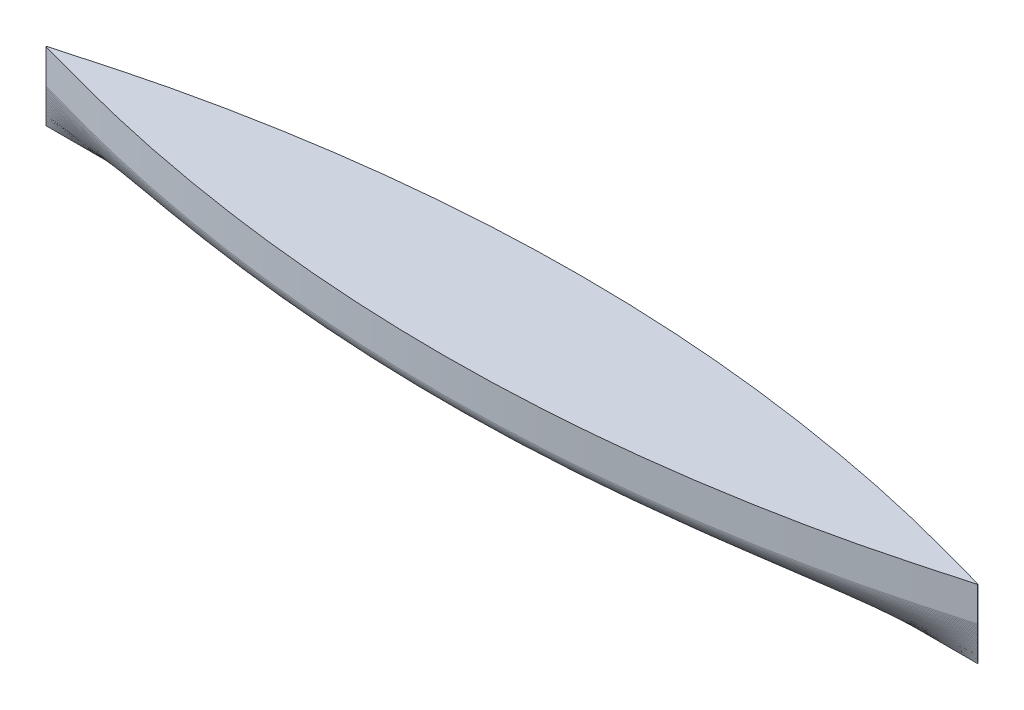
SolidWorks part; units mm, degrees
ref_plane "Plan de face" through (0, 0, 0) normal (0, 0, 1) x (1, 0, 0)
ref_plane "Plan de dessus" through (0, 0, 0) normal (0, 1, 0) x (1, 0, 0)
ref_plane "Plan de droite" through (0, 0, 0) normal (1, 0, 0) x (0, 0, -1)
ref_plane "Plan1" through (-48800, 0, 0) normal (1, 0, 0) x (0, 0, -1)
ref_plane "Plan2" through (-36600, 0, 0) normal (1, 0, 0) x (0, 0, -1)
ref_plane "Plan3" through (-24400, 0, 0) normal (1, 0, 0) x (0, 0, -1)
ref_plane "Plan4" through (-12200, 0, 0) normal (1, 0, 0) x (0, 0, -1)
ref_plane "Plan5" through (0, 0, 0) normal (1, 0, 0) x (0, 0, -1)
ref_plane "Plan6" through (12200, 0, 0) normal (1, 0, 0) x (0, 0, -1)
ref_plane "Plan7" through (24400, 0, 0) normal (1, 0, 0) x (0, 0, -1)
ref_plane "Plan8" through (36600, 0, 0) normal (1, 0, 0) x (0, 0, -1)
ref_plane "Plan9" through (48800, 0, 0) normal (1, 0, 0) x (0, 0, -1)
ref_plane "Plan10" through (-60900, 0, 0) normal (1, 0, 0) x (0, 0, -1)
ref_plane "Plan11" through (60900, 0, 0) normal (1, 0, 0) x (0, 0, -1)
sketch "Esquisse12" plane through (-60900, 0, 0) normal (1, 0, 0) x (0, 0, -1)
  line L0 (0, 0) -> (2.03, 150)
  line L1 (2.03, 150) -> (3.99, 300)
  line L2 (3.99, 300) -> (5.88, 450)
  line L3 (5.88, 450) -> (7.69, 600)
  line L4 (7.69, 600) -> (9.42, 750)
  line L5 (9.42, 750) -> (11.08, 900)
  line L6 (11.08, 900) -> (12.67, 1050)
  line L7 (12.67, 1050) -> (14.18, 1200)
  line L8 (14.18, 1200) -> (15.62, 1350)
  line L9 (15.62, 1350) -> (16.98, 1500)
  line L10 (16.98, 1500) -> (18.27, 1650)
  line L11 (18.27, 1650) -> (19.49, 1800)
  line L12 (19.49, 1800) -> (20.63, 1950)
  line L13 (20.63, 1950) -> (21.71, 2100)
  line L14 (21.71, 2100) -> (22.71, 2250)
  line L15 (22.71, 2250) -> (23.64, 2400)
  line L16 (23.64, 2400) -> (24.5, 2550)
  line L17 (24.5, 2550) -> (25.29, 2700)
  line L18 (25.29, 2700) -> (26, 2850)
  line L19 (26, 2850) -> (26.65, 3000)
  line L20 (26.65, 3000) -> (27.23, 3150)
  line L21 (27.23, 3150) -> (27.74, 3300)
  line L22 (27.74, 3300) -> (28.19, 3450)
  line L23 (28.19, 3450) -> (28.56, 3600)
  line L24 (28.56, 3600) -> (28.87, 3750)
  line L25 (28.87, 3750) -> (29.12, 3900)
  line L26 (29.12, 3900) -> (29.3, 4050)
  line L27 (29.3, 4050) -> (29.42, 4200)
  line L28 (29.42, 4200) -> (29.48, 4350)
  line L29 (29.48, 4350) -> (29.48, 4500)
  line L30 (29.48, 4500) -> (29.48, 4650)
  line L31 (29.48, 4650) -> (29.48, 4800)
  line L32 (29.48, 4800) -> (29.48, 4950)
  line L33 (29.48, 4950) -> (29.48, 5100)
  line L34 (29.48, 5100) -> (29.48, 5250)
  line L35 (29.48, 5250) -> (29.48, 5400)
  line L36 (29.48, 5400) -> (29.48, 5550)
  line L37 (29.48, 5550) -> (29.48, 5700)
  line L38 (29.48, 5700) -> (29.48, 5850)
  line L39 (29.48, 5850) -> (29.48, 6000)
  line L40 (29.48, 6000) -> (29.48, 6150)
  line L41 (29.48, 6150) -> (29.48, 6300)
  line L42 (29.48, 6300) -> (29.48, 6450)
  line L43 (29.48, 6450) -> (29.48, 6600)
  line L44 (29.48, 6600) -> (29.48, 6750)
  line L45 (29.48, 6750) -> (29.48, 6900)
  line L46 (29.48, 6900) -> (29.48, 7050)
  line L47 (29.48, 7050) -> (29.48, 7200)
  line L48 (29.48, 7200) -> (29.48, 7350)
  line L49 (29.48, 7350) -> (29.48, 7500)
  line L50 (29.48, 7500) -> (29.48, 7650)
  line L51 (29.48, 7650) -> (29.48, 7800)
  line L52 (29.48, 7800) -> (29.48, 7950)
  line L53 (29.48, 7950) -> (29.48, 8100)
  line L54 (29.48, 8100) -> (29.48, 8250)
  line L55 (29.48, 8250) -> (29.48, 8400)
  line L56 (29.48, 8400) -> (29.48, 8550)
  line L57 (29.48, 8550) -> (29.48, 8700)
  line L58 (29.48, 8700) -> (29.48, 8850)
  line L59 (29.48, 8850) -> (29.48, 9000)
  line L60 (29.48, 9000) -> (-29.48, 9000)
  line L61 (-29.48, 9000) -> (-29.48, 8850)
  line L62 (-29.48, 8850) -> (-29.48, 8700)
  line L63 (-29.48, 8700) -> (-29.48, 8550)
  line L64 (-29.48, 8550) -> (-29.48, 8400)
  line L65 (-29.48, 8400) -> (-29.48, 8250)
  line L66 (-29.48, 8250) -> (-29.48, 8100)
  line L67 (-29.48, 8100) -> (-29.48, 7950)
  line L68 (-29.48, 7950) -> (-29.48, 7800)
  line L69 (-29.48, 7800) -> (-29.48, 7650)
  line L70 (-29.48, 7650) -> (-29.48, 7500)
  line L71 (-29.48, 7500) -> (-29.48, 7350)
  line L72 (-29.48, 7350) -> (-29.48, 7200)
  line L73 (-29.48, 7200) -> (-29.48, 7050)
  line L74 (-29.48, 7050) -> (-29.48, 6900)
  line L75 (-29.48, 6900) -> (-29.48, 6750)
  line L76 (-29.48, 6750) -> (-29.48, 6600)
  line L77 (-29.48, 6600) -> (-29.48, 6450)
  line L78 (-29.48, 6450) -> (-29.48, 6300)
  line L79 (-29.48, 6300) -> (-29.48, 6150)
  line L80 (-29.48, 6150) -> (-29.48, 6000)
  line L81 (-29.48, 6000) -> (-29.48, 5850)
  line L82 (-29.48, 5850) -> (-29.48, 5700)
  line L83 (-29.48, 5700) -> (-29.48, 5550)
  line L84 (-29.48, 5550) -> (-29.48, 5400)
  line L85 (-29.48, 5400) -> (-29.48, 5250)
  line L86 (-29.48, 5250) -> (-29.48, 5100)
  line L87 (-29.48, 5100) -> (-29.48, 4950)
  line L88 (-29.48, 4950) -> (-29.48, 4800)
  line L89 (-29.48, 4800) -> (-29.48, 4650)
  line L90 (-29.48, 4650) -> (-29.48, 4500)
  line L91 (-29.48, 4500) -> (-29.48, 4350)
  line L92 (-29.48, 4350) -> (-29.42, 4200)
  line L93 (-29.42, 4200) -> (-29.3, 4050)
  line L94 (-29.3, 4050) -> (-29.12, 3900)
  line L95 (-29.12, 3900) -> (-28.87, 3750)
  line L96 (-28.87, 3750) -> (-28.56, 3600)
  line L97 (-28.56, 3600) -> (-28.19, 3450)
  line L98 (-28.19, 3450) -> (-27.74, 3300)
  line L99 (-27.74, 3300) -> (-27.23, 3150)
  line L100 (-27.23, 3150) -> (-26.65, 3000)
  line L101 (-26.65, 3000) -> (-26, 2850)
  line L102 (-26, 2850) -> (-25.29, 2700)
  line L103 (-25.29, 2700) -> (-24.5, 2550)
  line L104 (-24.5, 2550) -> (-23.64, 2400)
  line L105 (-23.64, 2400) -> (-22.71, 2250)
  line L106 (-22.71, 2250) -> (-21.71, 2100)
  line L107 (-21.71, 2100) -> (-20.63, 1950)
  line L108 (-20.63, 1950) -> (-19.49, 1800)
  line L109 (-19.49, 1800) -> (-18.27, 1650)
  line L110 (-18.27, 1650) -> (-16.98, 1500)
  line L111 (-16.98, 1500) -> (-15.62, 1350)
  line L112 (-15.62, 1350) -> (-14.18, 1200)
  line L113 (-14.18, 1200) -> (-12.67, 1050)
  line L114 (-12.67, 1050) -> (-11.08, 900)
  line L115 (-11.08, 900) -> (-9.42, 750)
  line L116 (-9.42, 750) -> (-7.69, 600)
  line L117 (-7.69, 600) -> (-5.88, 450)
  line L118 (-5.88, 450) -> (-3.99, 300)
  line L119 (-3.99, 300) -> (-2.03, 150)
  line L120 (-2.03, 150) -> (0, 0)
sketch "Esquisse15" plane through (60900, 0, 0) normal (1, 0, 0) x (0, 0, -1)
  line L0 (0, 0) -> (2.03, 150)
  line L1 (2.03, 150) -> (3.99, 300)
  line L2 (3.99, 300) -> (5.88, 450)
  line L3 (5.88, 450) -> (7.69, 600)
  line L4 (7.69, 600) -> (9.42, 750)
  line L5 (9.42, 750) -> (11.08, 900)
  line L6 (11.08, 900) -> (12.67, 1050)
  line L7 (12.67, 1050) -> (14.18, 1200)
  line L8 (14.18, 1200) -> (15.62, 1350)
  line L9 (15.62, 1350) -> (16.98, 1500)
  line L10 (16.98, 1500) -> (18.27, 1650)
  line L11 (18.27, 1650) -> (19.49, 1800)
  line L12 (19.49, 1800) -> (20.63, 1950)
  line L13 (20.63, 1950) -> (21.71, 2100)
  line L14 (21.71, 2100) -> (22.71, 2250)
  line L15 (22.71, 2250) -> (23.64, 2400)
  line L16 (23.64, 2400) -> (24.5, 2550)
  line L17 (24.5, 2550) -> (25.29, 2700)
  line L18 (25.29, 2700) -> (26, 2850)
  line L19 (26, 2850) -> (26.65, 3000)
  line L20 (26.65, 3000) -> (27.23, 3150)
  line L21 (27.23, 3150) -> (27.74, 3300)
  line L22 (27.74, 3300) -> (28.19, 3450)
  line L23 (28.19, 3450) -> (28.56, 3600)
  line L24 (28.56, 3600) -> (28.87, 3750)
  line L25 (28.87, 3750) -> (29.12, 3900)
  line L26 (29.12, 3900) -> (29.3, 4050)
  line L27 (29.3, 4050) -> (29.42, 4200)
  line L28 (29.42, 4200) -> (29.48, 4350)
  line L29 (29.48, 4350) -> (29.48, 4500)
  line L30 (29.48, 4500) -> (29.48, 4650)
  line L31 (29.48, 4650) -> (29.48, 4800)
  line L32 (29.48, 4800) -> (29.48, 4950)
  line L33 (29.48, 4950) -> (29.48, 5100)
  line L34 (29.48, 5100) -> (29.48, 5250)
  line L35 (29.48, 5250) -> (29.48, 5400)
  line L36 (29.48, 5400) -> (29.48, 5550)
  line L37 (29.48, 5550) -> (29.48, 5700)
  line L38 (29.48, 5700) -> (29.48, 5850)
  line L39 (29.48, 5850) -> (29.48, 6000)
  line L40 (29.48, 6000) -> (29.48, 6150)
  line L41 (29.48, 6150) -> (29.48, 6300)
  line L42 (29.48, 6300) -> (29.48, 6450)
  line L43 (29.48, 6450) -> (29.48, 6600)
  line L44 (29.48, 6600) -> (29.48, 6750)
  line L45 (29.48, 6750) -> (29.48, 6900)
  line L46 (29.48, 6900) -> (29.48, 7050)
  line L47 (29.48, 7050) -> (29.48, 7200)
  line L48 (29.48, 7200) -> (29.48, 7350)
  line L49 (29.48, 7350) -> (29.48, 7500)
  line L50 (29.48, 7500) -> (29.48, 7650)
  line L51 (29.48, 7650) -> (29.48, 7800)
  line L52 (29.48, 7800) -> (29.48, 7950)
  line L53 (29.48, 7950) -> (29.48, 8100)
  line L54 (29.48, 8100) -> (29.48, 8250)
  line L55 (29.48, 8250) -> (29.48, 8400)
  line L56 (29.48, 8400) -> (29.48, 8550)
  line L57 (29.48, 8550) -> (29.48, 8700)
  line L58 (29.48, 8700) -> (29.48, 8850)
  line L59 (29.48, 8850) -> (29.48, 9000)
  line L60 (29.48, 9000) -> (-29.48, 9000)
  line L61 (-29.48, 9000) -> (-29.48, 8850)
  line L62 (-29.48, 8850) -> (-29.48, 8700)
  line L63 (-29.48, 8700) -> (-29.48, 8550)
  line L64 (-29.48, 8550) -> (-29.48, 8400)
  line L65 (-29.48, 8400) -> (-29.48, 8250)
  line L66 (-29.48, 8250) -> (-29.48, 8100)
  line L67 (-29.48, 8100) -> (-29.48, 7950)
  line L68 (-29.48, 7950) -> (-29.48, 7800)
  line L69 (-29.48, 7800) -> (-29.48, 7650)
  line L70 (-29.48, 7650) -> (-29.48, 7500)
  line L71 (-29.48, 7500) -> (-29.48, 7350)
  line L72 (-29.48, 7350) -> (-29.48, 7200)
  line L73 (-29.48, 7200) -> (-29.48, 7050)
  line L74 (-29.48, 7050) -> (-29.48, 6900)
  line L75 (-29.48, 6900) -> (-29.48, 6750)
  line L76 (-29.48, 6750) -> (-29.48, 6600)
  line L77 (-29.48, 6600) -> (-29.48, 6450)
  line L78 (-29.48, 6450) -> (-29.48, 6300)
  line L79 (-29.48, 6300) -> (-29.48, 6150)
  line L80 (-29.48, 6150) -> (-29.48, 6000)
  line L81 (-29.48, 6000) -> (-29.48, 5850)
  line L82 (-29.48, 5850) -> (-29.48, 5700)
  line L83 (-29.48, 5700) -> (-29.48, 5550)
  line L84 (-29.48, 5550) -> (-29.48, 5400)
  line L85 (-29.48, 5400) -> (-29.48, 5250)
  line L86 (-29.48, 5250) -> (-29.48, 5100)
  line L87 (-29.48, 5100) -> (-29.48, 4950)
  line L88 (-29.48, 4950) -> (-29.48, 4800)
  line L89 (-29.48, 4800) -> (-29.48, 4650)
  line L90 (-29.48, 4650) -> (-29.48, 4500)
  line L91 (-29.48, 4500) -> (-29.48, 4350)
  line L92 (-29.48, 4350) -> (-29.42, 4200)
  line L93 (-29.42, 4200) -> (-29.3, 4050)
  line L94 (-29.3, 4050) -> (-29.12, 3900)
  line L95 (-29.12, 3900) -> (-28.87, 3750)
  line L96 (-28.87, 3750) -> (-28.56, 3600)
  line L97 (-28.56, 3600) -> (-28.19, 3450)
  line L98 (-28.19, 3450) -> (-27.74, 3300)
  line L99 (-27.74, 3300) -> (-27.23, 3150)
  line L100 (-27.23, 3150) -> (-26.65, 3000)
  line L101 (-26.65, 3000) -> (-26, 2850)
  line L102 (-26, 2850) -> (-25.29, 2700)
  line L103 (-25.29, 2700) -> (-24.5, 2550)
  line L104 (-24.5, 2550) -> (-23.64, 2400)
  line L105 (-23.64, 2400) -> (-22.71, 2250)
  line L106 (-22.71, 2250) -> (-21.71, 2100)
  line L107 (-21.71, 2100) -> (-20.63, 1950)
  line L108 (-20.63, 1950) -> (-19.49, 1800)
  line L109 (-19.49, 1800) -> (-18.27, 1650)
  line L110 (-18.27, 1650) -> (-16.98, 1500)
  line L111 (-16.98, 1500) -> (-15.62, 1350)
  line L112 (-15.62, 1350) -> (-14.18, 1200)
  line L113 (-14.18, 1200) -> (-12.67, 1050)
  line L114 (-12.67, 1050) -> (-11.08, 900)
  line L115 (-11.08, 900) -> (-9.42, 750)
  line L116 (-9.42, 750) -> (-7.69, 600)
  line L117 (-7.69, 600) -> (-5.88, 450)
  line L118 (-5.88, 450) -> (-3.99, 300)
  line L119 (-3.99, 300) -> (-2.03, 150)
  line L120 (-2.03, 150) -> (0, 0)
sketch "Esquisse1" plane through (-48800, 0, 0) normal (1, 0, 0) x (0, 0, -1)
  line L0 (0, 0) -> (223.61, 150)
  line L1 (223.61, 150) -> (438.92, 300)
  line L2 (438.92, 300) -> (645.97, 450)
  line L3 (645.97, 450) -> (844.77, 600)
  line L4 (844.77, 600) -> (1035.35, 750)
  line L5 (1035.35, 750) -> (1217.74, 900)
  line L6 (1217.74, 900) -> (1391.97, 1050)
  line L7 (1391.97, 1050) -> (1558.05, 1200)
  line L8 (1558.05, 1200) -> (1716.03, 1350)
  line L9 (1716.03, 1350) -> (1865.93, 1500)
  line L10 (1865.93, 1500) -> (2007.79, 1650)
  line L11 (2007.79, 1650) -> (2141.64, 1800)
  line L12 (2141.64, 1800) -> (2267.52, 1950)
  line L13 (2267.52, 1950) -> (2385.46, 2100)
  line L14 (2385.46, 2100) -> (2495.5, 2250)
  line L15 (2495.5, 2250) -> (2597.68, 2400)
  line L16 (2597.68, 2400) -> (2692.06, 2550)
  line L17 (2692.06, 2550) -> (2778.68, 2700)
  line L18 (2778.68, 2700) -> (2857.58, 2850)
  line L19 (2857.58, 2850) -> (2928.83, 3000)
  line L20 (2928.83, 3000) -> (2992.49, 3150)
  line L21 (2992.49, 3150) -> (3048.63, 3300)
  line L22 (3048.63, 3300) -> (3097.31, 3450)
  line L23 (3097.31, 3450) -> (3138.63, 3600)
  line L24 (3138.63, 3600) -> (3172.68, 3750)
  line L25 (3172.68, 3750) -> (3199.58, 3900)
  line L26 (3199.58, 3900) -> (3219.46, 4050)
  line L27 (3219.46, 4050) -> (3232.52, 4200)
  line L28 (3232.52, 4200) -> (3239.03, 4350)
  line L29 (3239.03, 4350) -> (3240, 4500)
  line L30 (3240, 4500) -> (3240, 4650)
  line L31 (3240, 4650) -> (3240, 4800)
  line L32 (3240, 4800) -> (3240, 4950)
  line L33 (3240, 4950) -> (3240, 5100)
  line L34 (3240, 5100) -> (3240, 5250)
  line L35 (3240, 5250) -> (3240, 5400)
  line L36 (3240, 5400) -> (3240, 5550)
  line L37 (3240, 5550) -> (3240, 5700)
  line L38 (3240, 5700) -> (3240, 5850)
  line L39 (3240, 5850) -> (3240, 6000)
  line L40 (3240, 6000) -> (3240, 6150)
  line L41 (3240, 6150) -> (3240, 6300)
  line L42 (3240, 6300) -> (3240, 6450)
  line L43 (3240, 6450) -> (3240, 6600)
  line L44 (3240, 6600) -> (3240, 6750)
  line L45 (3240, 6750) -> (3240, 6900)
  line L46 (3240, 6900) -> (3240, 7050)
  line L47 (3240, 7050) -> (3240, 7200)
  line L48 (3240, 7200) -> (3240, 7350)
  line L49 (3240, 7350) -> (3240, 7500)
  line L50 (3240, 7500) -> (3240, 7650)
  line L51 (3240, 7650) -> (3240, 7800)
  line L52 (3240, 7800) -> (3240, 7950)
  line L53 (3240, 7950) -> (3240, 8100)
  line L54 (3240, 8100) -> (3240, 8250)
  line L55 (3240, 8250) -> (3240, 8400)
  line L56 (3240, 8400) -> (3240, 8550)
  line L57 (3240, 8550) -> (3240, 8700)
  line L58 (3240, 8700) -> (3240, 8850)
  line L59 (3240, 8850) -> (3240, 9000)
  line L60 (3240, 9000) -> (-3240, 9000)
  line L61 (-3240, 9000) -> (-3240, 8850)
  line L62 (-3240, 8850) -> (-3240, 8700)
  line L63 (-3240, 8700) -> (-3240, 8550)
  line L64 (-3240, 8550) -> (-3240, 8400)
  line L65 (-3240, 8400) -> (-3240, 8250)
  line L66 (-3240, 8250) -> (-3240, 8100)
  line L67 (-3240, 8100) -> (-3240, 7950)
  line L68 (-3240, 7950) -> (-3240, 7800)
  line L69 (-3240, 7800) -> (-3240, 7650)
  line L70 (-3240, 7650) -> (-3240, 7500)
  line L71 (-3240, 7500) -> (-3240, 7350)
  line L72 (-3240, 7350) -> (-3240, 7200)
  line L73 (-3240, 7200) -> (-3240, 7050)
  line L74 (-3240, 7050) -> (-3240, 6900)
  line L75 (-3240, 6900) -> (-3240, 6750)
  line L76 (-3240, 6750) -> (-3240, 6600)
  line L77 (-3240, 6600) -> (-3240, 6450)
  line L78 (-3240, 6450) -> (-3240, 6300)
  line L79 (-3240, 6300) -> (-3240, 6150)
  line L80 (-3240, 6150) -> (-3240, 6000)
  line L81 (-3240, 6000) -> (-3240, 5850)
  line L82 (-3240, 5850) -> (-3240, 5700)
  line L83 (-3240, 5700) -> (-3240, 5550)
  line L84 (-3240, 5550) -> (-3240, 5400)
  line L85 (-3240, 5400) -> (-3240, 5250)
  line L86 (-3240, 5250) -> (-3240, 5100)
  line L87 (-3240, 5100) -> (-3240, 4950)
  line L88 (-3240, 4950) -> (-3240, 4800)
  line L89 (-3240, 4800) -> (-3240, 4650)
  line L90 (-3240, 4650) -> (-3240, 4500)
  line L91 (-3240, 4500) -> (-3239.03, 4350)
  line L92 (-3239.03, 4350) -> (-3232.52, 4200)
  line L93 (-3232.52, 4200) -> (-3219.46, 4050)
  line L94 (-3219.46, 4050) -> (-3199.58, 3900)
  line L95 (-3199.58, 3900) -> (-3172.68, 3750)
  line L96 (-3172.68, 3750) -> (-3138.63, 3600)
  line L97 (-3138.63, 3600) -> (-3097.31, 3450)
  line L98 (-3097.31, 3450) -> (-3048.63, 3300)
  line L99 (-3048.63, 3300) -> (-2992.49, 3150)
  line L100 (-2992.49, 3150) -> (-2928.83, 3000)
  line L101 (-2928.83, 3000) -> (-2857.58, 2850)
  line L102 (-2857.58, 2850) -> (-2778.68, 2700)
  line L103 (-2778.68, 2700) -> (-2692.06, 2550)
  line L104 (-2692.06, 2550) -> (-2597.68, 2400)
  line L105 (-2597.68, 2400) -> (-2495.5, 2250)
  line L106 (-2495.5, 2250) -> (-2385.46, 2100)
  line L107 (-2385.46, 2100) -> (-2267.52, 1950)
  line L108 (-2267.52, 1950) -> (-2141.64, 1800)
  line L109 (-2141.64, 1800) -> (-2007.79, 1650)
  line L110 (-2007.79, 1650) -> (-1865.93, 1500)
  line L111 (-1865.93, 1500) -> (-1716.03, 1350)
  line L112 (-1716.03, 1350) -> (-1558.05, 1200)
  line L113 (-1558.05, 1200) -> (-1391.97, 1050)
  line L114 (-1391.97, 1050) -> (-1217.74, 900)
  line L115 (-1217.74, 900) -> (-1035.35, 750)
  line L116 (-1035.35, 750) -> (-844.77, 600)
  line L117 (-844.77, 600) -> (-645.97, 450)
  line L118 (-645.97, 450) -> (-438.92, 300)
  line L119 (-438.92, 300) -> (-223.61, 150)
  line L120 (-223.61, 150) -> (0, 0)
sketch "Esquisse2" plane through (-36600, 0, 0) normal (1, 0, 0) x (0, 0, -1)
  line L0 (0, 0) -> (397.53, 150)
  line L1 (397.53, 150) -> (780.31, 300)
  line L2 (780.31, 300) -> (1148.39, 450)
  line L3 (1148.39, 450) -> (1501.82, 600)
  line L4 (1501.82, 600) -> (1840.63, 750)
  line L5 (1840.63, 750) -> (2164.88, 900)
  line L6 (2164.88, 900) -> (2474.61, 1050)
  line L7 (2474.61, 1050) -> (2769.87, 1200)
  line L8 (2769.87, 1200) -> (3050.72, 1350)
  line L9 (3050.72, 1350) -> (3317.22, 1500)
  line L10 (3317.22, 1500) -> (3569.41, 1650)
  line L11 (3569.41, 1650) -> (3807.36, 1800)
  line L12 (3807.36, 1800) -> (4031.14, 1950)
  line L13 (4031.14, 1950) -> (4240.81, 2100)
  line L14 (4240.81, 2100) -> (4436.44, 2250)
  line L15 (4436.44, 2250) -> (4618.1, 2400)
  line L16 (4618.1, 2400) -> (4785.89, 2550)
  line L17 (4785.89, 2550) -> (4939.87, 2700)
  line L18 (4939.87, 2700) -> (5080.15, 2850)
  line L19 (5080.15, 2850) -> (5206.82, 3000)
  line L20 (5206.82, 3000) -> (5319.99, 3150)
  line L21 (5319.99, 3150) -> (5419.78, 3300)
  line L22 (5419.78, 3300) -> (5506.33, 3450)
  line L23 (5506.33, 3450) -> (5579.79, 3600)
  line L24 (5579.79, 3600) -> (5640.32, 3750)
  line L25 (5640.32, 3750) -> (5688.14, 3900)
  line L26 (5688.14, 3900) -> (5723.49, 4050)
  line L27 (5723.49, 4050) -> (5746.7, 4200)
  line L28 (5746.7, 4200) -> (5758.27, 4350)
  line L29 (5758.27, 4350) -> (5760, 4500)
  line L30 (5760, 4500) -> (5760, 4650)
  line L31 (5760, 4650) -> (5760, 4800)
  line L32 (5760, 4800) -> (5760, 4950)
  line L33 (5760, 4950) -> (5760, 5100)
  line L34 (5760, 5100) -> (5760, 5250)
  line L35 (5760, 5250) -> (5760, 5400)
  line L36 (5760, 5400) -> (5760, 5550)
  line L37 (5760, 5550) -> (5760, 5700)
  line L38 (5760, 5700) -> (5760, 5850)
  line L39 (5760, 5850) -> (5760, 6000)
  line L40 (5760, 6000) -> (5760, 6150)
  line L41 (5760, 6150) -> (5760, 6300)
  line L42 (5760, 6300) -> (5760, 6450)
  line L43 (5760, 6450) -> (5760, 6600)
  line L44 (5760, 6600) -> (5760, 6750)
  line L45 (5760, 6750) -> (5760, 6900)
  line L46 (5760, 6900) -> (5760, 7050)
  line L47 (5760, 7050) -> (5760, 7200)
  line L48 (5760, 7200) -> (5760, 7350)
  line L49 (5760, 7350) -> (5760, 7500)
  line L50 (5760, 7500) -> (5760, 7650)
  line L51 (5760, 7650) -> (5760, 7800)
  line L52 (5760, 7800) -> (5760, 7950)
  line L53 (5760, 7950) -> (5760, 8100)
  line L54 (5760, 8100) -> (5760, 8250)
  line L55 (5760, 8250) -> (5760, 8400)
  line L56 (5760, 8400) -> (5760, 8550)
  line L57 (5760, 8550) -> (5760, 8700)
  line L58 (5760, 8700) -> (5760, 8850)
  line L59 (5760, 8850) -> (5760, 9000)
  line L60 (5760, 9000) -> (-5760, 9000)
  line L61 (-5760, 9000) -> (-5760, 8850)
  line L62 (-5760, 8850) -> (-5760, 8700)
  line L63 (-5760, 8700) -> (-5760, 8550)
  line L64 (-5760, 8550) -> (-5760, 8400)
  line L65 (-5760, 8400) -> (-5760, 8250)
  line L66 (-5760, 8250) -> (-5760, 8100)
  line L67 (-5760, 8100) -> (-5760, 7950)
  line L68 (-5760, 7950) -> (-5760, 7800)
  line L69 (-5760, 7800) -> (-5760, 7650)
  line L70 (-5760, 7650) -> (-5760, 7500)
  line L71 (-5760, 7500) -> (-5760, 7350)
  line L72 (-5760, 7350) -> (-5760, 7200)
  line L73 (-5760, 7200) -> (-5760, 7050)
  line L74 (-5760, 7050) -> (-5760, 6900)
  line L75 (-5760, 6900) -> (-5760, 6750)
  line L76 (-5760, 6750) -> (-5760, 6600)
  line L77 (-5760, 6600) -> (-5760, 6450)
  line L78 (-5760, 6450) -> (-5760, 6300)
  line L79 (-5760, 6300) -> (-5760, 6150)
  line L80 (-5760, 6150) -> (-5760, 6000)
  line L81 (-5760, 6000) -> (-5760, 5850)
  line L82 (-5760, 5850) -> (-5760, 5700)
  line L83 (-5760, 5700) -> (-5760, 5550)
  line L84 (-5760, 5550) -> (-5760, 5400)
  line L85 (-5760, 5400) -> (-5760, 5250)
  line L86 (-5760, 5250) -> (-5760, 5100)
  line L87 (-5760, 5100) -> (-5760, 4950)
  line L88 (-5760, 4950) -> (-5760, 4800)
  line L89 (-5760, 4800) -> (-5760, 4650)
  line L90 (-5760, 4650) -> (-5760, 4500)
  line L91 (-5760, 4500) -> (-5758.27, 4350)
  line L92 (-5758.27, 4350) -> (-5746.7, 4200)
  line L93 (-5746.7, 4200) -> (-5723.49, 4050)
  line L94 (-5723.49, 4050) -> (-5688.14, 3900)
  line L95 (-5688.14, 3900) -> (-5640.32, 3750)
  line L96 (-5640.32, 3750) -> (-5579.79, 3600)
  line L97 (-5579.79, 3600) -> (-5506.33, 3450)
  line L98 (-5506.33, 3450) -> (-5419.78, 3300)
  line L99 (-5419.78, 3300) -> (-5319.99, 3150)
  line L100 (-5319.99, 3150) -> (-5206.82, 3000)
  line L101 (-5206.82, 3000) -> (-5080.15, 2850)
  line L102 (-5080.15, 2850) -> (-4939.87, 2700)
  line L103 (-4939.87, 2700) -> (-4785.89, 2550)
  line L104 (-4785.89, 2550) -> (-4618.1, 2400)
  line L105 (-4618.1, 2400) -> (-4436.44, 2250)
  line L106 (-4436.44, 2250) -> (-4240.81, 2100)
  line L107 (-4240.81, 2100) -> (-4031.14, 1950)
  line L108 (-4031.14, 1950) -> (-3807.36, 1800)
  line L109 (-3807.36, 1800) -> (-3569.41, 1650)
  line L110 (-3569.41, 1650) -> (-3317.22, 1500)
  line L111 (-3317.22, 1500) -> (-3050.72, 1350)
  line L112 (-3050.72, 1350) -> (-2769.87, 1200)
  line L113 (-2769.87, 1200) -> (-2474.61, 1050)
  line L114 (-2474.61, 1050) -> (-2164.88, 900)
  line L115 (-2164.88, 900) -> (-1840.63, 750)
  line L116 (-1840.63, 750) -> (-1501.82, 600)
  line L117 (-1501.82, 600) -> (-1148.39, 450)
  line L118 (-1148.39, 450) -> (-780.31, 300)
  line L119 (-780.31, 300) -> (-397.53, 150)
  line L120 (-397.53, 150) -> (0, 0)
sketch "Esquisse3" plane through (-24400, 0, 0) normal (1, 0, 0) x (0, 0, -1)
  line L0 (0, 0) -> (521.75, 150)
  line L1 (521.75, 150) -> (1024.16, 300)
  line L2 (1024.16, 300) -> (1507.26, 450)
  line L3 (1507.26, 450) -> (1971.13, 600)
  line L4 (1971.13, 600) -> (2415.82, 750)
  line L5 (2415.82, 750) -> (2841.4, 900)
  line L6 (2841.4, 900) -> (3247.92, 1050)
  line L7 (3247.92, 1050) -> (3635.45, 1200)
  line L8 (3635.45, 1200) -> (4004.07, 1350)
  line L9 (4004.07, 1350) -> (4353.85, 1500)
  line L10 (4353.85, 1500) -> (4684.85, 1650)
  line L11 (4684.85, 1650) -> (4997.16, 1800)
  line L12 (4997.16, 1800) -> (5290.87, 1950)
  line L13 (5290.87, 1950) -> (5566.06, 2100)
  line L14 (5566.06, 2100) -> (5822.83, 2250)
  line L15 (5822.83, 2250) -> (6061.26, 2400)
  line L16 (6061.26, 2400) -> (6281.48, 2550)
  line L17 (6281.48, 2550) -> (6483.58, 2700)
  line L18 (6483.58, 2700) -> (6667.69, 2850)
  line L19 (6667.69, 2850) -> (6833.95, 3000)
  line L20 (6833.95, 3000) -> (6982.49, 3150)
  line L21 (6982.49, 3150) -> (7113.47, 3300)
  line L22 (7113.47, 3300) -> (7227.06, 3450)
  line L23 (7227.06, 3450) -> (7323.47, 3600)
  line L24 (7323.47, 3600) -> (7402.92, 3750)
  line L25 (7402.92, 3750) -> (7465.68, 3900)
  line L26 (7465.68, 3900) -> (7512.08, 4050)
  line L27 (7512.08, 4050) -> (7542.55, 4200)
  line L28 (7542.55, 4200) -> (7557.73, 4350)
  line L29 (7557.73, 4350) -> (7560, 4500)
  line L30 (7560, 4500) -> (7560, 4650)
  line L31 (7560, 4650) -> (7560, 4800)
  line L32 (7560, 4800) -> (7560, 4950)
  line L33 (7560, 4950) -> (7560, 5100)
  line L34 (7560, 5100) -> (7560, 5250)
  line L35 (7560, 5250) -> (7560, 5400)
  line L36 (7560, 5400) -> (7560, 5550)
  line L37 (7560, 5550) -> (7560, 5700)
  line L38 (7560, 5700) -> (7560, 5850)
  line L39 (7560, 5850) -> (7560, 6000)
  line L40 (7560, 6000) -> (7560, 6150)
  line L41 (7560, 6150) -> (7560, 6300)
  line L42 (7560, 6300) -> (7560, 6450)
  line L43 (7560, 6450) -> (7560, 6600)
  line L44 (7560, 6600) -> (7560, 6750)
  line L45 (7560, 6750) -> (7560, 6900)
  line L46 (7560, 6900) -> (7560, 7050)
  line L47 (7560, 7050) -> (7560, 7200)
  line L48 (7560, 7200) -> (7560, 7350)
  line L49 (7560, 7350) -> (7560, 7500)
  line L50 (7560, 7500) -> (7560, 7650)
  line L51 (7560, 7650) -> (7560, 7800)
  line L52 (7560, 7800) -> (7560, 7950)
  line L53 (7560, 7950) -> (7560, 8100)
  line L54 (7560, 8100) -> (7560, 8250)
  line L55 (7560, 8250) -> (7560, 8400)
  line L56 (7560, 8400) -> (7560, 8550)
  line L57 (7560, 8550) -> (7560, 8700)
  line L58 (7560, 8700) -> (7560, 8850)
  line L59 (7560, 8850) -> (7560, 9000)
  line L60 (7560, 9000) -> (-7560, 9000)
  line L61 (-7560, 9000) -> (-7560, 8850)
  line L62 (-7560, 8850) -> (-7560, 8700)
  line L63 (-7560, 8700) -> (-7560, 8550)
  line L64 (-7560, 8550) -> (-7560, 8400)
  line L65 (-7560, 8400) -> (-7560, 8250)
  line L66 (-7560, 8250) -> (-7560, 8100)
  line L67 (-7560, 8100) -> (-7560, 7950)
  line L68 (-7560, 7950) -> (-7560, 7800)
  line L69 (-7560, 7800) -> (-7560, 7650)
  line L70 (-7560, 7650) -> (-7560, 7500)
  line L71 (-7560, 7500) -> (-7560, 7350)
  line L72 (-7560, 7350) -> (-7560, 7200)
  line L73 (-7560, 7200) -> (-7560, 7050)
  line L74 (-7560, 7050) -> (-7560, 6900)
  line L75 (-7560, 6900) -> (-7560, 6750)
  line L76 (-7560, 6750) -> (-7560, 6600)
  line L77 (-7560, 6600) -> (-7560, 6450)
  line L78 (-7560, 6450) -> (-7560, 6300)
  line L79 (-7560, 6300) -> (-7560, 6150)
  line L80 (-7560, 6150) -> (-7560, 6000)
  line L81 (-7560, 6000) -> (-7560, 5850)
  line L82 (-7560, 5850) -> (-7560, 5700)
  line L83 (-7560, 5700) -> (-7560, 5550)
  line L84 (-7560, 5550) -> (-7560, 5400)
  line L85 (-7560, 5400) -> (-7560, 5250)
  line L86 (-7560, 5250) -> (-7560, 5100)
  line L87 (-7560, 5100) -> (-7560, 4950)
  line L88 (-7560, 4950) -> (-7560, 4800)
  line L89 (-7560, 4800) -> (-7560, 4650)
  line L90 (-7560, 4650) -> (-7560, 4500)
  line L91 (-7560, 4500) -> (-7557.73, 4350)
  line L92 (-7557.73, 4350) -> (-7542.55, 4200)
  line L93 (-7542.55, 4200) -> (-7512.08, 4050)
  line L94 (-7512.08, 4050) -> (-7465.68, 3900)
  line L95 (-7465.68, 3900) -> (-7402.92, 3750)
  line L96 (-7402.92, 3750) -> (-7323.47, 3600)
  line L97 (-7323.47, 3600) -> (-7227.06, 3450)
  line L98 (-7227.06, 3450) -> (-7113.47, 3300)
  line L99 (-7113.47, 3300) -> (-6982.49, 3150)
  line L100 (-6982.49, 3150) -> (-6833.95, 3000)
  line L101 (-6833.95, 3000) -> (-6667.69, 2850)
  line L102 (-6667.69, 2850) -> (-6483.58, 2700)
  line L103 (-6483.58, 2700) -> (-6281.48, 2550)
  line L104 (-6281.48, 2550) -> (-6061.26, 2400)
  line L105 (-6061.26, 2400) -> (-5822.83, 2250)
  line L106 (-5822.83, 2250) -> (-5566.06, 2100)
  line L107 (-5566.06, 2100) -> (-5290.87, 1950)
  line L108 (-5290.87, 1950) -> (-4997.16, 1800)
  line L109 (-4997.16, 1800) -> (-4684.85, 1650)
  line L110 (-4684.85, 1650) -> (-4353.85, 1500)
  line L111 (-4353.85, 1500) -> (-4004.07, 1350)
  line L112 (-4004.07, 1350) -> (-3635.45, 1200)
  line L113 (-3635.45, 1200) -> (-3247.92, 1050)
  line L114 (-3247.92, 1050) -> (-2841.4, 900)
  line L115 (-2841.4, 900) -> (-2415.82, 750)
  line L116 (-2415.82, 750) -> (-1971.13, 600)
  line L117 (-1971.13, 600) -> (-1507.26, 450)
  line L118 (-1507.26, 450) -> (-1024.16, 300)
  line L119 (-1024.16, 300) -> (-521.75, 150)
  line L120 (-521.75, 150) -> (0, 0)
sketch "Esquisse4" plane through (-12200, 0, 0) normal (1, 0, 0) x (0, 0, -1)
  line L0 (0, 0) -> (596.29, 150)
  line L1 (596.29, 150) -> (1170.46, 300)
  line L2 (1170.46, 300) -> (1722.59, 450)
  line L3 (1722.59, 450) -> (2252.72, 600)
  line L4 (2252.72, 600) -> (2760.94, 750)
  line L5 (2760.94, 750) -> (3247.31, 900)
  line L6 (3247.31, 900) -> (3711.91, 1050)
  line L7 (3711.91, 1050) -> (4154.81, 1200)
  line L8 (4154.81, 1200) -> (4576.08, 1350)
  line L9 (4576.08, 1350) -> (4975.82, 1500)
  line L10 (4975.82, 1500) -> (5354.11, 1650)
  line L11 (5354.11, 1650) -> (5711.04, 1800)
  line L12 (5711.04, 1800) -> (6046.71, 1950)
  line L13 (6046.71, 1950) -> (6361.21, 2100)
  line L14 (6361.21, 2100) -> (6654.66, 2250)
  line L15 (6654.66, 2250) -> (6927.16, 2400)
  line L16 (6927.16, 2400) -> (7178.83, 2550)
  line L17 (7178.83, 2550) -> (7409.8, 2700)
  line L18 (7409.8, 2700) -> (7620.22, 2850)
  line L19 (7620.22, 2850) -> (7810.23, 3000)
  line L20 (7810.23, 3000) -> (7979.98, 3150)
  line L21 (7979.98, 3150) -> (8129.67, 3300)
  line L22 (8129.67, 3300) -> (8259.5, 3450)
  line L23 (8259.5, 3450) -> (8369.68, 3600)
  line L24 (8369.68, 3600) -> (8460.48, 3750)
  line L25 (8460.48, 3750) -> (8532.2, 3900)
  line L26 (8532.2, 3900) -> (8585.23, 4050)
  line L27 (8585.23, 4050) -> (8620.06, 4200)
  line L28 (8620.06, 4200) -> (8637.41, 4350)
  line L29 (8637.41, 4350) -> (8640, 4500)
  line L30 (8640, 4500) -> (8640, 4650)
  line L31 (8640, 4650) -> (8640, 4800)
  line L32 (8640, 4800) -> (8640, 4950)
  line L33 (8640, 4950) -> (8640, 5100)
  line L34 (8640, 5100) -> (8640, 5250)
  line L35 (8640, 5250) -> (8640, 5400)
  line L36 (8640, 5400) -> (8640, 5550)
  line L37 (8640, 5550) -> (8640, 5700)
  line L38 (8640, 5700) -> (8640, 5850)
  line L39 (8640, 5850) -> (8640, 6000)
  line L40 (8640, 6000) -> (8640, 6150)
  line L41 (8640, 6150) -> (8640, 6300)
  line L42 (8640, 6300) -> (8640, 6450)
  line L43 (8640, 6450) -> (8640, 6600)
  line L44 (8640, 6600) -> (8640, 6750)
  line L45 (8640, 6750) -> (8640, 6900)
  line L46 (8640, 6900) -> (8640, 7050)
  line L47 (8640, 7050) -> (8640, 7200)
  line L48 (8640, 7200) -> (8640, 7350)
  line L49 (8640, 7350) -> (8640, 7500)
  line L50 (8640, 7500) -> (8640, 7650)
  line L51 (8640, 7650) -> (8640, 7800)
  line L52 (8640, 7800) -> (8640, 7950)
  line L53 (8640, 7950) -> (8640, 8100)
  line L54 (8640, 8100) -> (8640, 8250)
  line L55 (8640, 8250) -> (8640, 8400)
  line L56 (8640, 8400) -> (8640, 8550)
  line L57 (8640, 8550) -> (8640, 8700)
  line L58 (8640, 8700) -> (8640, 8850)
  line L59 (8640, 8850) -> (8640, 9000)
  line L60 (8640, 9000) -> (-8640, 9000)
  line L61 (-8640, 9000) -> (-8640, 8850)
  line L62 (-8640, 8850) -> (-8640, 8700)
  line L63 (-8640, 8700) -> (-8640, 8550)
  line L64 (-8640, 8550) -> (-8640, 8400)
  line L65 (-8640, 8400) -> (-8640, 8250)
  line L66 (-8640, 8250) -> (-8640, 8100)
  line L67 (-8640, 8100) -> (-8640, 7950)
  line L68 (-8640, 7950) -> (-8640, 7800)
  line L69 (-8640, 7800) -> (-8640, 7650)
  line L70 (-8640, 7650) -> (-8640, 7500)
  line L71 (-8640, 7500) -> (-8640, 7350)
  line L72 (-8640, 7350) -> (-8640, 7200)
  line L73 (-8640, 7200) -> (-8640, 7050)
  line L74 (-8640, 7050) -> (-8640, 6900)
  line L75 (-8640, 6900) -> (-8640, 6750)
  line L76 (-8640, 6750) -> (-8640, 6600)
  line L77 (-8640, 6600) -> (-8640, 6450)
  line L78 (-8640, 6450) -> (-8640, 6300)
  line L79 (-8640, 6300) -> (-8640, 6150)
  line L80 (-8640, 6150) -> (-8640, 6000)
  line L81 (-8640, 6000) -> (-8640, 5850)
  line L82 (-8640, 5850) -> (-8640, 5700)
  line L83 (-8640, 5700) -> (-8640, 5550)
  line L84 (-8640, 5550) -> (-8640, 5400)
  line L85 (-8640, 5400) -> (-8640, 5250)
  line L86 (-8640, 5250) -> (-8640, 5100)
  line L87 (-8640, 5100) -> (-8640, 4950)
  line L88 (-8640, 4950) -> (-8640, 4800)
  line L89 (-8640, 4800) -> (-8640, 4650)
  line L90 (-8640, 4650) -> (-8640, 4500)
  line L91 (-8640, 4500) -> (-8637.41, 4350)
  line L92 (-8637.41, 4350) -> (-8620.06, 4200)
  line L93 (-8620.06, 4200) -> (-8585.23, 4050)
  line L94 (-8585.23, 4050) -> (-8532.2, 3900)
  line L95 (-8532.2, 3900) -> (-8460.48, 3750)
  line L96 (-8460.48, 3750) -> (-8369.68, 3600)
  line L97 (-8369.68, 3600) -> (-8259.5, 3450)
  line L98 (-8259.5, 3450) -> (-8129.67, 3300)
  line L99 (-8129.67, 3300) -> (-7979.98, 3150)
  line L100 (-7979.98, 3150) -> (-7810.23, 3000)
  line L101 (-7810.23, 3000) -> (-7620.22, 2850)
  line L102 (-7620.22, 2850) -> (-7409.8, 2700)
  line L103 (-7409.8, 2700) -> (-7178.83, 2550)
  line L104 (-7178.83, 2550) -> (-6927.16, 2400)
  line L105 (-6927.16, 2400) -> (-6654.66, 2250)
  line L106 (-6654.66, 2250) -> (-6361.21, 2100)
  line L107 (-6361.21, 2100) -> (-6046.71, 1950)
  line L108 (-6046.71, 1950) -> (-5711.04, 1800)
  line L109 (-5711.04, 1800) -> (-5354.11, 1650)
  line L110 (-5354.11, 1650) -> (-4975.82, 1500)
  line L111 (-4975.82, 1500) -> (-4576.08, 1350)
  line L112 (-4576.08, 1350) -> (-4154.81, 1200)
  line L113 (-4154.81, 1200) -> (-3711.91, 1050)
  line L114 (-3711.91, 1050) -> (-3247.31, 900)
  line L115 (-3247.31, 900) -> (-2760.94, 750)
  line L116 (-2760.94, 750) -> (-2252.72, 600)
  line L117 (-2252.72, 600) -> (-1722.59, 450)
  line L118 (-1722.59, 450) -> (-1170.46, 300)
  line L119 (-1170.46, 300) -> (-596.29, 150)
  line L120 (-596.29, 150) -> (0, 0)
sketch "Esquisse5" plane through (0, 0, 0) normal (1, 0, 0) x (0, 0, -1)
  line L0 (0, 0) -> (621.14, 150)
  line L1 (621.14, 150) -> (1219.23, 300)
  line L2 (1219.23, 300) -> (1794.36, 450)
  line L3 (1794.36, 450) -> (2346.59, 600)
  line L4 (2346.59, 600) -> (2875.98, 750)
  line L5 (2875.98, 750) -> (3382.62, 900)
  line L6 (3382.62, 900) -> (3866.57, 1050)
  line L7 (3866.57, 1050) -> (4327.92, 1200)
  line L8 (4327.92, 1200) -> (4766.75, 1350)
  line L9 (4766.75, 1350) -> (5183.15, 1500)
  line L10 (5183.15, 1500) -> (5577.2, 1650)
  line L11 (5577.2, 1650) -> (5949.01, 1800)
  line L12 (5949.01, 1800) -> (6298.66, 1950)
  line L13 (6298.66, 1950) -> (6626.26, 2100)
  line L14 (6626.26, 2100) -> (6931.94, 2250)
  line L15 (6931.94, 2250) -> (7215.79, 2400)
  line L16 (7215.79, 2400) -> (7477.95, 2550)
  line L17 (7477.95, 2550) -> (7718.55, 2700)
  line L18 (7718.55, 2700) -> (7937.73, 2850)
  line L19 (7937.73, 2850) -> (8135.65, 3000)
  line L20 (8135.65, 3000) -> (8312.48, 3150)
  line L21 (8312.48, 3150) -> (8468.41, 3300)
  line L22 (8468.41, 3300) -> (8603.64, 3450)
  line L23 (8603.64, 3450) -> (8718.42, 3600)
  line L24 (8718.42, 3600) -> (8813, 3750)
  line L25 (8813, 3750) -> (8887.71, 3900)
  line L26 (8887.71, 3900) -> (8942.95, 4050)
  line L27 (8942.95, 4050) -> (8979.23, 4200)
  line L28 (8979.23, 4200) -> (8997.3, 4350)
  line L29 (8997.3, 4350) -> (9000, 4500)
  line L30 (9000, 4500) -> (9000, 4650)
  line L31 (9000, 4650) -> (9000, 4800)
  line L32 (9000, 4800) -> (9000, 4950)
  line L33 (9000, 4950) -> (9000, 5100)
  line L34 (9000, 5100) -> (9000, 5250)
  line L35 (9000, 5250) -> (9000, 5400)
  line L36 (9000, 5400) -> (9000, 5550)
  line L37 (9000, 5550) -> (9000, 5700)
  line L38 (9000, 5700) -> (9000, 5850)
  line L39 (9000, 5850) -> (9000, 6000)
  line L40 (9000, 6000) -> (9000, 6150)
  line L41 (9000, 6150) -> (9000, 6300)
  line L42 (9000, 6300) -> (9000, 6450)
  line L43 (9000, 6450) -> (9000, 6600)
  line L44 (9000, 6600) -> (9000, 6750)
  line L45 (9000, 6750) -> (9000, 6900)
  line L46 (9000, 6900) -> (9000, 7050)
  line L47 (9000, 7050) -> (9000, 7200)
  line L48 (9000, 7200) -> (9000, 7350)
  line L49 (9000, 7350) -> (9000, 7500)
  line L50 (9000, 7500) -> (9000, 7650)
  line L51 (9000, 7650) -> (9000, 7800)
  line L52 (9000, 7800) -> (9000, 7950)
  line L53 (9000, 7950) -> (9000, 8100)
  line L54 (9000, 8100) -> (9000, 8250)
  line L55 (9000, 8250) -> (9000, 8400)
  line L56 (9000, 8400) -> (9000, 8550)
  line L57 (9000, 8550) -> (9000, 8700)
  line L58 (9000, 8700) -> (9000, 8850)
  line L59 (9000, 8850) -> (9000, 9000)
  line L60 (9000, 9000) -> (-9000, 9000)
  line L61 (-9000, 9000) -> (-9000, 8850)
  line L62 (-9000, 8850) -> (-9000, 8700)
  line L63 (-9000, 8700) -> (-9000, 8550)
  line L64 (-9000, 8550) -> (-9000, 8400)
  line L65 (-9000, 8400) -> (-9000, 8250)
  line L66 (-9000, 8250) -> (-9000, 8100)
  line L67 (-9000, 8100) -> (-9000, 7950)
  line L68 (-9000, 7950) -> (-9000, 7800)
  line L69 (-9000, 7800) -> (-9000, 7650)
  line L70 (-9000, 7650) -> (-9000, 7500)
  line L71 (-9000, 7500) -> (-9000, 7350)
  line L72 (-9000, 7350) -> (-9000, 7200)
  line L73 (-9000, 7200) -> (-9000, 7050)
  line L74 (-9000, 7050) -> (-9000, 6900)
  line L75 (-9000, 6900) -> (-9000, 6750)
  line L76 (-9000, 6750) -> (-9000, 6600)
  line L77 (-9000, 6600) -> (-9000, 6450)
  line L78 (-9000, 6450) -> (-9000, 6300)
  line L79 (-9000, 6300) -> (-9000, 6150)
  line L80 (-9000, 6150) -> (-9000, 6000)
  line L81 (-9000, 6000) -> (-9000, 5850)
  line L82 (-9000, 5850) -> (-9000, 5700)
  line L83 (-9000, 5700) -> (-9000, 5550)
  line L84 (-9000, 5550) -> (-9000, 5400)
  line L85 (-9000, 5400) -> (-9000, 5250)
  line L86 (-9000, 5250) -> (-9000, 5100)
  line L87 (-9000, 5100) -> (-9000, 4950)
  line L88 (-9000, 4950) -> (-9000, 4800)
  line L89 (-9000, 4800) -> (-9000, 4650)
  line L90 (-9000, 4650) -> (-9000, 4500)
  line L91 (-9000, 4500) -> (-8997.3, 4350)
  line L92 (-8997.3, 4350) -> (-8979.23, 4200)
  line L93 (-8979.23, 4200) -> (-8942.95, 4050)
  line L94 (-8942.95, 4050) -> (-8887.71, 3900)
  line L95 (-8887.71, 3900) -> (-8813, 3750)
  line L96 (-8813, 3750) -> (-8718.42, 3600)
  line L97 (-8718.42, 3600) -> (-8603.64, 3450)
  line L98 (-8603.64, 3450) -> (-8468.41, 3300)
  line L99 (-8468.41, 3300) -> (-8312.48, 3150)
  line L100 (-8312.48, 3150) -> (-8135.65, 3000)
  line L101 (-8135.65, 3000) -> (-7937.73, 2850)
  line L102 (-7937.73, 2850) -> (-7718.55, 2700)
  line L103 (-7718.55, 2700) -> (-7477.95, 2550)
  line L104 (-7477.95, 2550) -> (-7215.79, 2400)
  line L105 (-7215.79, 2400) -> (-6931.94, 2250)
  line L106 (-6931.94, 2250) -> (-6626.26, 2100)
  line L107 (-6626.26, 2100) -> (-6298.66, 1950)
  line L108 (-6298.66, 1950) -> (-5949.01, 1800)
  line L109 (-5949.01, 1800) -> (-5577.2, 1650)
  line L110 (-5577.2, 1650) -> (-5183.15, 1500)
  line L111 (-5183.15, 1500) -> (-4766.75, 1350)
  line L112 (-4766.75, 1350) -> (-4327.92, 1200)
  line L113 (-4327.92, 1200) -> (-3866.57, 1050)
  line L114 (-3866.57, 1050) -> (-3382.62, 900)
  line L115 (-3382.62, 900) -> (-2875.98, 750)
  line L116 (-2875.98, 750) -> (-2346.59, 600)
  line L117 (-2346.59, 600) -> (-1794.36, 450)
  line L118 (-1794.36, 450) -> (-1219.23, 300)
  line L119 (-1219.23, 300) -> (-621.14, 150)
  line L120 (-621.14, 150) -> (0, 0)
sketch "Esquisse6" plane through (12200, 0, 0) normal (1, 0, 0) x (0, 0, -1)
  line L0 (0, 0) -> (596.29, 150)
  line L1 (596.29, 150) -> (1170.46, 300)
  line L2 (1170.46, 300) -> (1722.59, 450)
  line L3 (1722.59, 450) -> (2252.72, 600)
  line L4 (2252.72, 600) -> (2760.94, 750)
  line L5 (2760.94, 750) -> (3247.31, 900)
  line L6 (3247.31, 900) -> (3711.91, 1050)
  line L7 (3711.91, 1050) -> (4154.81, 1200)
  line L8 (4154.81, 1200) -> (4576.08, 1350)
  line L9 (4576.08, 1350) -> (4975.82, 1500)
  line L10 (4975.82, 1500) -> (5354.11, 1650)
  line L11 (5354.11, 1650) -> (5711.04, 1800)
  line L12 (5711.04, 1800) -> (6046.71, 1950)
  line L13 (6046.71, 1950) -> (6361.21, 2100)
  line L14 (6361.21, 2100) -> (6654.66, 2250)
  line L15 (6654.66, 2250) -> (6927.16, 2400)
  line L16 (6927.16, 2400) -> (7178.83, 2550)
  line L17 (7178.83, 2550) -> (7409.8, 2700)
  line L18 (7409.8, 2700) -> (7620.22, 2850)
  line L19 (7620.22, 2850) -> (7810.23, 3000)
  line L20 (7810.23, 3000) -> (7979.98, 3150)
  line L21 (7979.98, 3150) -> (8129.67, 3300)
  line L22 (8129.67, 3300) -> (8259.5, 3450)
  line L23 (8259.5, 3450) -> (8369.68, 3600)
  line L24 (8369.68, 3600) -> (8460.48, 3750)
  line L25 (8460.48, 3750) -> (8532.2, 3900)
  line L26 (8532.2, 3900) -> (8585.23, 4050)
  line L27 (8585.23, 4050) -> (8620.06, 4200)
  line L28 (8620.06, 4200) -> (8637.41, 4350)
  line L29 (8637.41, 4350) -> (8640, 4500)
  line L30 (8640, 4500) -> (8640, 4650)
  line L31 (8640, 4650) -> (8640, 4800)
  line L32 (8640, 4800) -> (8640, 4950)
  line L33 (8640, 4950) -> (8640, 5100)
  line L34 (8640, 5100) -> (8640, 5250)
  line L35 (8640, 5250) -> (8640, 5400)
  line L36 (8640, 5400) -> (8640, 5550)
  line L37 (8640, 5550) -> (8640, 5700)
  line L38 (8640, 5700) -> (8640, 5850)
  line L39 (8640, 5850) -> (8640, 6000)
  line L40 (8640, 6000) -> (8640, 6150)
  line L41 (8640, 6150) -> (8640, 6300)
  line L42 (8640, 6300) -> (8640, 6450)
  line L43 (8640, 6450) -> (8640, 6600)
  line L44 (8640, 6600) -> (8640, 6750)
  line L45 (8640, 6750) -> (8640, 6900)
  line L46 (8640, 6900) -> (8640, 7050)
  line L47 (8640, 7050) -> (8640, 7200)
  line L48 (8640, 7200) -> (8640, 7350)
  line L49 (8640, 7350) -> (8640, 7500)
  line L50 (8640, 7500) -> (8640, 7650)
  line L51 (8640, 7650) -> (8640, 7800)
  line L52 (8640, 7800) -> (8640, 7950)
  line L53 (8640, 7950) -> (8640, 8100)
  line L54 (8640, 8100) -> (8640, 8250)
  line L55 (8640, 8250) -> (8640, 8400)
  line L56 (8640, 8400) -> (8640, 8550)
  line L57 (8640, 8550) -> (8640, 8700)
  line L58 (8640, 8700) -> (8640, 8850)
  line L59 (8640, 8850) -> (8640, 9000)
  line L60 (8640, 9000) -> (-8640, 9000)
  line L61 (-8640, 9000) -> (-8640, 8850)
  line L62 (-8640, 8850) -> (-8640, 8700)
  line L63 (-8640, 8700) -> (-8640, 8550)
  line L64 (-8640, 8550) -> (-8640, 8400)
  line L65 (-8640, 8400) -> (-8640, 8250)
  line L66 (-8640, 8250) -> (-8640, 8100)
  line L67 (-8640, 8100) -> (-8640, 7950)
  line L68 (-8640, 7950) -> (-8640, 7800)
  line L69 (-8640, 7800) -> (-8640, 7650)
  line L70 (-8640, 7650) -> (-8640, 7500)
  line L71 (-8640, 7500) -> (-8640, 7350)
  line L72 (-8640, 7350) -> (-8640, 7200)
  line L73 (-8640, 7200) -> (-8640, 7050)
  line L74 (-8640, 7050) -> (-8640, 6900)
  line L75 (-8640, 6900) -> (-8640, 6750)
  line L76 (-8640, 6750) -> (-8640, 6600)
  line L77 (-8640, 6600) -> (-8640, 6450)
  line L78 (-8640, 6450) -> (-8640, 6300)
  line L79 (-8640, 6300) -> (-8640, 6150)
  line L80 (-8640, 6150) -> (-8640, 6000)
  line L81 (-8640, 6000) -> (-8640, 5850)
  line L82 (-8640, 5850) -> (-8640, 5700)
  line L83 (-8640, 5700) -> (-8640, 5550)
  line L84 (-8640, 5550) -> (-8640, 5400)
  line L85 (-8640, 5400) -> (-8640, 5250)
  line L86 (-8640, 5250) -> (-8640, 5100)
  line L87 (-8640, 5100) -> (-8640, 4950)
  line L88 (-8640, 4950) -> (-8640, 4800)
  line L89 (-8640, 4800) -> (-8640, 4650)
  line L90 (-8640, 4650) -> (-8640, 4500)
  line L91 (-8640, 4500) -> (-8637.41, 4350)
  line L92 (-8637.41, 4350) -> (-8620.06, 4200)
  line L93 (-8620.06, 4200) -> (-8585.23, 4050)
  line L94 (-8585.23, 4050) -> (-8532.2, 3900)
  line L95 (-8532.2, 3900) -> (-8460.48, 3750)
  line L96 (-8460.48, 3750) -> (-8369.68, 3600)
  line L97 (-8369.68, 3600) -> (-8259.5, 3450)
  line L98 (-8259.5, 3450) -> (-8129.67, 3300)
  line L99 (-8129.67, 3300) -> (-7979.98, 3150)
  line L100 (-7979.98, 3150) -> (-7810.23, 3000)
  line L101 (-7810.23, 3000) -> (-7620.22, 2850)
  line L102 (-7620.22, 2850) -> (-7409.8, 2700)
  line L103 (-7409.8, 2700) -> (-7178.83, 2550)
  line L104 (-7178.83, 2550) -> (-6927.16, 2400)
  line L105 (-6927.16, 2400) -> (-6654.66, 2250)
  line L106 (-6654.66, 2250) -> (-6361.21, 2100)
  line L107 (-6361.21, 2100) -> (-6046.71, 1950)
  line L108 (-6046.71, 1950) -> (-5711.04, 1800)
  line L109 (-5711.04, 1800) -> (-5354.11, 1650)
  line L110 (-5354.11, 1650) -> (-4975.82, 1500)
  line L111 (-4975.82, 1500) -> (-4576.08, 1350)
  line L112 (-4576.08, 1350) -> (-4154.81, 1200)
  line L113 (-4154.81, 1200) -> (-3711.91, 1050)
  line L114 (-3711.91, 1050) -> (-3247.31, 900)
  line L115 (-3247.31, 900) -> (-2760.94, 750)
  line L116 (-2760.94, 750) -> (-2252.72, 600)
  line L117 (-2252.72, 600) -> (-1722.59, 450)
  line L118 (-1722.59, 450) -> (-1170.46, 300)
  line L119 (-1170.46, 300) -> (-596.29, 150)
  line L120 (-596.29, 150) -> (0, 0)
sketch "Esquisse7" plane through (24400, 0, 0) normal (1, 0, 0) x (0, 0, -1)
  line L0 (0, 0) -> (521.75, 150)
  line L1 (521.75, 150) -> (1024.16, 300)
  line L2 (1024.16, 300) -> (1507.26, 450)
  line L3 (1507.26, 450) -> (1971.13, 600)
  line L4 (1971.13, 600) -> (2415.82, 750)
  line L5 (2415.82, 750) -> (2841.4, 900)
  line L6 (2841.4, 900) -> (3247.92, 1050)
  line L7 (3247.92, 1050) -> (3635.45, 1200)
  line L8 (3635.45, 1200) -> (4004.07, 1350)
  line L9 (4004.07, 1350) -> (4353.85, 1500)
  line L10 (4353.85, 1500) -> (4684.85, 1650)
  line L11 (4684.85, 1650) -> (4997.16, 1800)
  line L12 (4997.16, 1800) -> (5290.87, 1950)
  line L13 (5290.87, 1950) -> (5566.06, 2100)
  line L14 (5566.06, 2100) -> (5822.83, 2250)
  line L15 (5822.83, 2250) -> (6061.26, 2400)
  line L16 (6061.26, 2400) -> (6281.48, 2550)
  line L17 (6281.48, 2550) -> (6483.58, 2700)
  line L18 (6483.58, 2700) -> (6667.69, 2850)
  line L19 (6667.69, 2850) -> (6833.95, 3000)
  line L20 (6833.95, 3000) -> (6982.49, 3150)
  line L21 (6982.49, 3150) -> (7113.47, 3300)
  line L22 (7113.47, 3300) -> (7227.06, 3450)
  line L23 (7227.06, 3450) -> (7323.47, 3600)
  line L24 (7323.47, 3600) -> (7402.92, 3750)
  line L25 (7402.92, 3750) -> (7465.68, 3900)
  line L26 (7465.68, 3900) -> (7512.08, 4050)
  line L27 (7512.08, 4050) -> (7542.55, 4200)
  line L28 (7542.55, 4200) -> (7557.73, 4350)
  line L29 (7557.73, 4350) -> (7560, 4500)
  line L30 (7560, 4500) -> (7560, 4650)
  line L31 (7560, 4650) -> (7560, 4800)
  line L32 (7560, 4800) -> (7560, 4950)
  line L33 (7560, 4950) -> (7560, 5100)
  line L34 (7560, 5100) -> (7560, 5250)
  line L35 (7560, 5250) -> (7560, 5400)
  line L36 (7560, 5400) -> (7560, 5550)
  line L37 (7560, 5550) -> (7560, 5700)
  line L38 (7560, 5700) -> (7560, 5850)
  line L39 (7560, 5850) -> (7560, 6000)
  line L40 (7560, 6000) -> (7560, 6150)
  line L41 (7560, 6150) -> (7560, 6300)
  line L42 (7560, 6300) -> (7560, 6450)
  line L43 (7560, 6450) -> (7560, 6600)
  line L44 (7560, 6600) -> (7560, 6750)
  line L45 (7560, 6750) -> (7560, 6900)
  line L46 (7560, 6900) -> (7560, 7050)
  line L47 (7560, 7050) -> (7560, 7200)
  line L48 (7560, 7200) -> (7560, 7350)
  line L49 (7560, 7350) -> (7560, 7500)
  line L50 (7560, 7500) -> (7560, 7650)
  line L51 (7560, 7650) -> (7560, 7800)
  line L52 (7560, 7800) -> (7560, 7950)
  line L53 (7560, 7950) -> (7560, 8100)
  line L54 (7560, 8100) -> (7560, 8250)
  line L55 (7560, 8250) -> (7560, 8400)
  line L56 (7560, 8400) -> (7560, 8550)
  line L57 (7560, 8550) -> (7560, 8700)
  line L58 (7560, 8700) -> (7560, 8850)
  line L59 (7560, 8850) -> (7560, 9000)
  line L60 (7560, 9000) -> (-7560, 9000)
  line L61 (-7560, 9000) -> (-7560, 8850)
  line L62 (-7560, 8850) -> (-7560, 8700)
  line L63 (-7560, 8700) -> (-7560, 8550)
  line L64 (-7560, 8550) -> (-7560, 8400)
  line L65 (-7560, 8400) -> (-7560, 8250)
  line L66 (-7560, 8250) -> (-7560, 8100)
  line L67 (-7560, 8100) -> (-7560, 7950)
  line L68 (-7560, 7950) -> (-7560, 7800)
  line L69 (-7560, 7800) -> (-7560, 7650)
  line L70 (-7560, 7650) -> (-7560, 7500)
  line L71 (-7560, 7500) -> (-7560, 7350)
  line L72 (-7560, 7350) -> (-7560, 7200)
  line L73 (-7560, 7200) -> (-7560, 7050)
  line L74 (-7560, 7050) -> (-7560, 6900)
  line L75 (-7560, 6900) -> (-7560, 6750)
  line L76 (-7560, 6750) -> (-7560, 6600)
  line L77 (-7560, 6600) -> (-7560, 6450)
  line L78 (-7560, 6450) -> (-7560, 6300)
  line L79 (-7560, 6300) -> (-7560, 6150)
  line L80 (-7560, 6150) -> (-7560, 6000)
  line L81 (-7560, 6000) -> (-7560, 5850)
  line L82 (-7560, 5850) -> (-7560, 5700)
  line L83 (-7560, 5700) -> (-7560, 5550)
  line L84 (-7560, 5550) -> (-7560, 5400)
  line L85 (-7560, 5400) -> (-7560, 5250)
  line L86 (-7560, 5250) -> (-7560, 5100)
  line L87 (-7560, 5100) -> (-7560, 4950)
  line L88 (-7560, 4950) -> (-7560, 4800)
  line L89 (-7560, 4800) -> (-7560, 4650)
  line L90 (-7560, 4650) -> (-7560, 4500)
  line L91 (-7560, 4500) -> (-7557.73, 4350)
  line L92 (-7557.73, 4350) -> (-7542.55, 4200)
  line L93 (-7542.55, 4200) -> (-7512.08, 4050)
  line L94 (-7512.08, 4050) -> (-7465.68, 3900)
  line L95 (-7465.68, 3900) -> (-7402.92, 3750)
  line L96 (-7402.92, 3750) -> (-7323.47, 3600)
  line L97 (-7323.47, 3600) -> (-7227.06, 3450)
  line L98 (-7227.06, 3450) -> (-7113.47, 3300)
  line L99 (-7113.47, 3300) -> (-6982.49, 3150)
  line L100 (-6982.49, 3150) -> (-6833.95, 3000)
  line L101 (-6833.95, 3000) -> (-6667.69, 2850)
  line L102 (-6667.69, 2850) -> (-6483.58, 2700)
  line L103 (-6483.58, 2700) -> (-6281.48, 2550)
  line L104 (-6281.48, 2550) -> (-6061.26, 2400)
  line L105 (-6061.26, 2400) -> (-5822.83, 2250)
  line L106 (-5822.83, 2250) -> (-5566.06, 2100)
  line L107 (-5566.06, 2100) -> (-5290.87, 1950)
  line L108 (-5290.87, 1950) -> (-4997.16, 1800)
  line L109 (-4997.16, 1800) -> (-4684.85, 1650)
  line L110 (-4684.85, 1650) -> (-4353.85, 1500)
  line L111 (-4353.85, 1500) -> (-4004.07, 1350)
  line L112 (-4004.07, 1350) -> (-3635.45, 1200)
  line L113 (-3635.45, 1200) -> (-3247.92, 1050)
  line L114 (-3247.92, 1050) -> (-2841.4, 900)
  line L115 (-2841.4, 900) -> (-2415.82, 750)
  line L116 (-2415.82, 750) -> (-1971.13, 600)
  line L117 (-1971.13, 600) -> (-1507.26, 450)
  line L118 (-1507.26, 450) -> (-1024.16, 300)
  line L119 (-1024.16, 300) -> (-521.75, 150)
  line L120 (-521.75, 150) -> (0, 0)
sketch "Esquisse8" plane through (36600, 0, 0) normal (1, 0, 0) x (0, 0, -1)
  line L0 (0, 0) -> (397.53, 150)
  line L1 (397.53, 150) -> (780.31, 300)
  line L2 (780.31, 300) -> (1148.39, 450)
  line L3 (1148.39, 450) -> (1501.82, 600)
  line L4 (1501.82, 600) -> (1840.63, 750)
  line L5 (1840.63, 750) -> (2164.88, 900)
  line L6 (2164.88, 900) -> (2474.61, 1050)
  line L7 (2474.61, 1050) -> (2769.87, 1200)
  line L8 (2769.87, 1200) -> (3050.72, 1350)
  line L9 (3050.72, 1350) -> (3317.22, 1500)
  line L10 (3317.22, 1500) -> (3569.41, 1650)
  line L11 (3569.41, 1650) -> (3807.36, 1800)
  line L12 (3807.36, 1800) -> (4031.14, 1950)
  line L13 (4031.14, 1950) -> (4240.81, 2100)
  line L14 (4240.81, 2100) -> (4436.44, 2250)
  line L15 (4436.44, 2250) -> (4618.1, 2400)
  line L16 (4618.1, 2400) -> (4785.89, 2550)
  line L17 (4785.89, 2550) -> (4939.87, 2700)
  line L18 (4939.87, 2700) -> (5080.15, 2850)
  line L19 (5080.15, 2850) -> (5206.82, 3000)
  line L20 (5206.82, 3000) -> (5319.99, 3150)
  line L21 (5319.99, 3150) -> (5419.78, 3300)
  line L22 (5419.78, 3300) -> (5506.33, 3450)
  line L23 (5506.33, 3450) -> (5579.79, 3600)
  line L24 (5579.79, 3600) -> (5640.32, 3750)
  line L25 (5640.32, 3750) -> (5688.14, 3900)
  line L26 (5688.14, 3900) -> (5723.49, 4050)
  line L27 (5723.49, 4050) -> (5746.7, 4200)
  line L28 (5746.7, 4200) -> (5758.27, 4350)
  line L29 (5758.27, 4350) -> (5760, 4500)
  line L30 (5760, 4500) -> (5760, 4650)
  line L31 (5760, 4650) -> (5760, 4800)
  line L32 (5760, 4800) -> (5760, 4950)
  line L33 (5760, 4950) -> (5760, 5100)
  line L34 (5760, 5100) -> (5760, 5250)
  line L35 (5760, 5250) -> (5760, 5400)
  line L36 (5760, 5400) -> (5760, 5550)
  line L37 (5760, 5550) -> (5760, 5700)
  line L38 (5760, 5700) -> (5760, 5850)
  line L39 (5760, 5850) -> (5760, 6000)
  line L40 (5760, 6000) -> (5760, 6150)
  line L41 (5760, 6150) -> (5760, 6300)
  line L42 (5760, 6300) -> (5760, 6450)
  line L43 (5760, 6450) -> (5760, 6600)
  line L44 (5760, 6600) -> (5760, 6750)
  line L45 (5760, 6750) -> (5760, 6900)
  line L46 (5760, 6900) -> (5760, 7050)
  line L47 (5760, 7050) -> (5760, 7200)
  line L48 (5760, 7200) -> (5760, 7350)
  line L49 (5760, 7350) -> (5760, 7500)
  line L50 (5760, 7500) -> (5760, 7650)
  line L51 (5760, 7650) -> (5760, 7800)
  line L52 (5760, 7800) -> (5760, 7950)
  line L53 (5760, 7950) -> (5760, 8100)
  line L54 (5760, 8100) -> (5760, 8250)
  line L55 (5760, 8250) -> (5760, 8400)
  line L56 (5760, 8400) -> (5760, 8550)
  line L57 (5760, 8550) -> (5760, 8700)
  line L58 (5760, 8700) -> (5760, 8850)
  line L59 (5760, 8850) -> (5760, 9000)
  line L60 (5760, 9000) -> (-5760, 9000)
  line L61 (-5760, 9000) -> (-5760, 8850)
  line L62 (-5760, 8850) -> (-5760, 8700)
  line L63 (-5760, 8700) -> (-5760, 8550)
  line L64 (-5760, 8550) -> (-5760, 8400)
  line L65 (-5760, 8400) -> (-5760, 8250)
  line L66 (-5760, 8250) -> (-5760, 8100)
  line L67 (-5760, 8100) -> (-5760, 7950)
  line L68 (-5760, 7950) -> (-5760, 7800)
  line L69 (-5760, 7800) -> (-5760, 7650)
  line L70 (-5760, 7650) -> (-5760, 7500)
  line L71 (-5760, 7500) -> (-5760, 7350)
  line L72 (-5760, 7350) -> (-5760, 7200)
  line L73 (-5760, 7200) -> (-5760, 7050)
  line L74 (-5760, 7050) -> (-5760, 6900)
  line L75 (-5760, 6900) -> (-5760, 6750)
  line L76 (-5760, 6750) -> (-5760, 6600)
  line L77 (-5760, 6600) -> (-5760, 6450)
  line L78 (-5760, 6450) -> (-5760, 6300)
  line L79 (-5760, 6300) -> (-5760, 6150)
  line L80 (-5760, 6150) -> (-5760, 6000)
  line L81 (-5760, 6000) -> (-5760, 5850)
  line L82 (-5760, 5850) -> (-5760, 5700)
  line L83 (-5760, 5700) -> (-5760, 5550)
  line L84 (-5760, 5550) -> (-5760, 5400)
  line L85 (-5760, 5400) -> (-5760, 5250)
  line L86 (-5760, 5250) -> (-5760, 5100)
  line L87 (-5760, 5100) -> (-5760, 4950)
  line L88 (-5760, 4950) -> (-5760, 4800)
  line L89 (-5760, 4800) -> (-5760, 4650)
  line L90 (-5760, 4650) -> (-5760, 4500)
  line L91 (-5760, 4500) -> (-5758.27, 4350)
  line L92 (-5758.27, 4350) -> (-5746.7, 4200)
  line L93 (-5746.7, 4200) -> (-5723.49, 4050)
  line L94 (-5723.49, 4050) -> (-5688.14, 3900)
  line L95 (-5688.14, 3900) -> (-5640.32, 3750)
  line L96 (-5640.32, 3750) -> (-5579.79, 3600)
  line L97 (-5579.79, 3600) -> (-5506.33, 3450)
  line L98 (-5506.33, 3450) -> (-5419.78, 3300)
  line L99 (-5419.78, 3300) -> (-5319.99, 3150)
  line L100 (-5319.99, 3150) -> (-5206.82, 3000)
  line L101 (-5206.82, 3000) -> (-5080.15, 2850)
  line L102 (-5080.15, 2850) -> (-4939.87, 2700)
  line L103 (-4939.87, 2700) -> (-4785.89, 2550)
  line L104 (-4785.89, 2550) -> (-4618.1, 2400)
  line L105 (-4618.1, 2400) -> (-4436.44, 2250)
  line L106 (-4436.44, 2250) -> (-4240.81, 2100)
  line L107 (-4240.81, 2100) -> (-4031.14, 1950)
  line L108 (-4031.14, 1950) -> (-3807.36, 1800)
  line L109 (-3807.36, 1800) -> (-3569.41, 1650)
  line L110 (-3569.41, 1650) -> (-3317.22, 1500)
  line L111 (-3317.22, 1500) -> (-3050.72, 1350)
  line L112 (-3050.72, 1350) -> (-2769.87, 1200)
  line L113 (-2769.87, 1200) -> (-2474.61, 1050)
  line L114 (-2474.61, 1050) -> (-2164.88, 900)
  line L115 (-2164.88, 900) -> (-1840.63, 750)
  line L116 (-1840.63, 750) -> (-1501.82, 600)
  line L117 (-1501.82, 600) -> (-1148.39, 450)
  line L118 (-1148.39, 450) -> (-780.31, 300)
  line L119 (-780.31, 300) -> (-397.53, 150)
  line L120 (-397.53, 150) -> (0, 0)
sketch "Esquisse9" plane through (48800, 0, 0) normal (1, 0, 0) x (0, 0, -1)
  line L0 (0, 0) -> (223.61, 150)
  line L1 (223.61, 150) -> (438.92, 300)
  line L2 (438.92, 300) -> (645.97, 450)
  line L3 (645.97, 450) -> (844.77, 600)
  line L4 (844.77, 600) -> (1035.35, 750)
  line L5 (1035.35, 750) -> (1217.74, 900)
  line L6 (1217.74, 900) -> (1391.97, 1050)
  line L7 (1391.97, 1050) -> (1558.05, 1200)
  line L8 (1558.05, 1200) -> (1716.03, 1350)
  line L9 (1716.03, 1350) -> (1865.93, 1500)
  line L10 (1865.93, 1500) -> (2007.79, 1650)
  line L11 (2007.79, 1650) -> (2141.64, 1800)
  line L12 (2141.64, 1800) -> (2267.52, 1950)
  line L13 (2267.52, 1950) -> (2385.46, 2100)
  line L14 (2385.46, 2100) -> (2495.5, 2250)
  line L15 (2495.5, 2250) -> (2597.68, 2400)
  line L16 (2597.68, 2400) -> (2692.06, 2550)
  line L17 (2692.06, 2550) -> (2778.68, 2700)
  line L18 (2778.68, 2700) -> (2857.58, 2850)
  line L19 (2857.58, 2850) -> (2928.83, 3000)
  line L20 (2928.83, 3000) -> (2992.49, 3150)
  line L21 (2992.49, 3150) -> (3048.63, 3300)
  line L22 (3048.63, 3300) -> (3097.31, 3450)
  line L23 (3097.31, 3450) -> (3138.63, 3600)
  line L24 (3138.63, 3600) -> (3172.68, 3750)
  line L25 (3172.68, 3750) -> (3199.58, 3900)
  line L26 (3199.58, 3900) -> (3219.46, 4050)
  line L27 (3219.46, 4050) -> (3232.52, 4200)
  line L28 (3232.52, 4200) -> (3239.03, 4350)
  line L29 (3239.03, 4350) -> (3240, 4500)
  line L30 (3240, 4500) -> (3240, 4650)
  line L31 (3240, 4650) -> (3240, 4800)
  line L32 (3240, 4800) -> (3240, 4950)
  line L33 (3240, 4950) -> (3240, 5100)
  line L34 (3240, 5100) -> (3240, 5250)
  line L35 (3240, 5250) -> (3240, 5400)
  line L36 (3240, 5400) -> (3240, 5550)
  line L37 (3240, 5550) -> (3240, 5700)
  line L38 (3240, 5700) -> (3240, 5850)
  line L39 (3240, 5850) -> (3240, 6000)
  line L40 (3240, 6000) -> (3240, 6150)
  line L41 (3240, 6150) -> (3240, 6300)
  line L42 (3240, 6300) -> (3240, 6450)
  line L43 (3240, 6450) -> (3240, 6600)
  line L44 (3240, 6600) -> (3240, 6750)
  line L45 (3240, 6750) -> (3240, 6900)
  line L46 (3240, 6900) -> (3240, 7050)
  line L47 (3240, 7050) -> (3240, 7200)
  line L48 (3240, 7200) -> (3240, 7350)
  line L49 (3240, 7350) -> (3240, 7500)
  line L50 (3240, 7500) -> (3240, 7650)
  line L51 (3240, 7650) -> (3240, 7800)
  line L52 (3240, 7800) -> (3240, 7950)
  line L53 (3240, 7950) -> (3240, 8100)
  line L54 (3240, 8100) -> (3240, 8250)
  line L55 (3240, 8250) -> (3240, 8400)
  line L56 (3240, 8400) -> (3240, 8550)
  line L57 (3240, 8550) -> (3240, 8700)
  line L58 (3240, 8700) -> (3240, 8850)
  line L59 (3240, 8850) -> (3240, 9000)
  line L60 (3240, 9000) -> (-3240, 9000)
  line L61 (-3240, 9000) -> (-3240, 8850)
  line L62 (-3240, 8850) -> (-3240, 8700)
  line L63 (-3240, 8700) -> (-3240, 8550)
  line L64 (-3240, 8550) -> (-3240, 8400)
  line L65 (-3240, 8400) -> (-3240, 8250)
  line L66 (-3240, 8250) -> (-3240, 8100)
  line L67 (-3240, 8100) -> (-3240, 7950)
  line L68 (-3240, 7950) -> (-3240, 7800)
  line L69 (-3240, 7800) -> (-3240, 7650)
  line L70 (-3240, 7650) -> (-3240, 7500)
  line L71 (-3240, 7500) -> (-3240, 7350)
  line L72 (-3240, 7350) -> (-3240, 7200)
  line L73 (-3240, 7200) -> (-3240, 7050)
  line L74 (-3240, 7050) -> (-3240, 6900)
  line L75 (-3240, 6900) -> (-3240, 6750)
  line L76 (-3240, 6750) -> (-3240, 6600)
  line L77 (-3240, 6600) -> (-3240, 6450)
  line L78 (-3240, 6450) -> (-3240, 6300)
  line L79 (-3240, 6300) -> (-3240, 6150)
  line L80 (-3240, 6150) -> (-3240, 6000)
  line L81 (-3240, 6000) -> (-3240, 5850)
  line L82 (-3240, 5850) -> (-3240, 5700)
  line L83 (-3240, 5700) -> (-3240, 5550)
  line L84 (-3240, 5550) -> (-3240, 5400)
  line L85 (-3240, 5400) -> (-3240, 5250)
  line L86 (-3240, 5250) -> (-3240, 5100)
  line L87 (-3240, 5100) -> (-3240, 4950)
  line L88 (-3240, 4950) -> (-3240, 4800)
  line L89 (-3240, 4800) -> (-3240, 4650)
  line L90 (-3240, 4650) -> (-3240, 4500)
  line L91 (-3240, 4500) -> (-3239.03, 4350)
  line L92 (-3239.03, 4350) -> (-3232.52, 4200)
  line L93 (-3232.52, 4200) -> (-3219.46, 4050)
  line L94 (-3219.46, 4050) -> (-3199.58, 3900)
  line L95 (-3199.58, 3900) -> (-3172.68, 3750)
  line L96 (-3172.68, 3750) -> (-3138.63, 3600)
  line L97 (-3138.63, 3600) -> (-3097.31, 3450)
  line L98 (-3097.31, 3450) -> (-3048.63, 3300)
  line L99 (-3048.63, 3300) -> (-2992.49, 3150)
  line L100 (-2992.49, 3150) -> (-2928.83, 3000)
  line L101 (-2928.83, 3000) -> (-2857.58, 2850)
  line L102 (-2857.58, 2850) -> (-2778.68, 2700)
  line L103 (-2778.68, 2700) -> (-2692.06, 2550)
  line L104 (-2692.06, 2550) -> (-2597.68, 2400)
  line L105 (-2597.68, 2400) -> (-2495.5, 2250)
  line L106 (-2495.5, 2250) -> (-2385.46, 2100)
  line L107 (-2385.46, 2100) -> (-2267.52, 1950)
  line L108 (-2267.52, 1950) -> (-2141.64, 1800)
  line L109 (-2141.64, 1800) -> (-2007.79, 1650)
  line L110 (-2007.79, 1650) -> (-1865.93, 1500)
  line L111 (-1865.93, 1500) -> (-1716.03, 1350)
  line L112 (-1716.03, 1350) -> (-1558.05, 1200)
  line L113 (-1558.05, 1200) -> (-1391.97, 1050)
  line L114 (-1391.97, 1050) -> (-1217.74, 900)
  line L115 (-1217.74, 900) -> (-1035.35, 750)
  line L116 (-1035.35, 750) -> (-844.77, 600)
  line L117 (-844.77, 600) -> (-645.97, 450)
  line L118 (-645.97, 450) -> (-438.92, 300)
  line L119 (-438.92, 300) -> (-223.61, 150)
  line L120 (-223.61, 150) -> (0, 0)
loft "Lissage1" add profiles "Esquisse12", "Esquisse1", "Esquisse2", "Esquisse3", "Esquisse4", "Esquisse5", "Esquisse6", "Esquisse7", "Esquisse8", "Esquisse9", "Esquisse15" connector at (-60900, 9000, -29.48) connector at (-48800, 9000, -3240) connector at (-36600, 9000, -5760) connector at (-24400, 9000, -7560) connector at (-12200, 9000, -8640) connector at (0, 9000, -9000) connector at (12200, 9000, -8640) connector at (24400, 9000, -7560) connector at (36600, 9000, -5760) connector at (48800, 9000, -3240) connector at (60900, 9000, -29.48)
